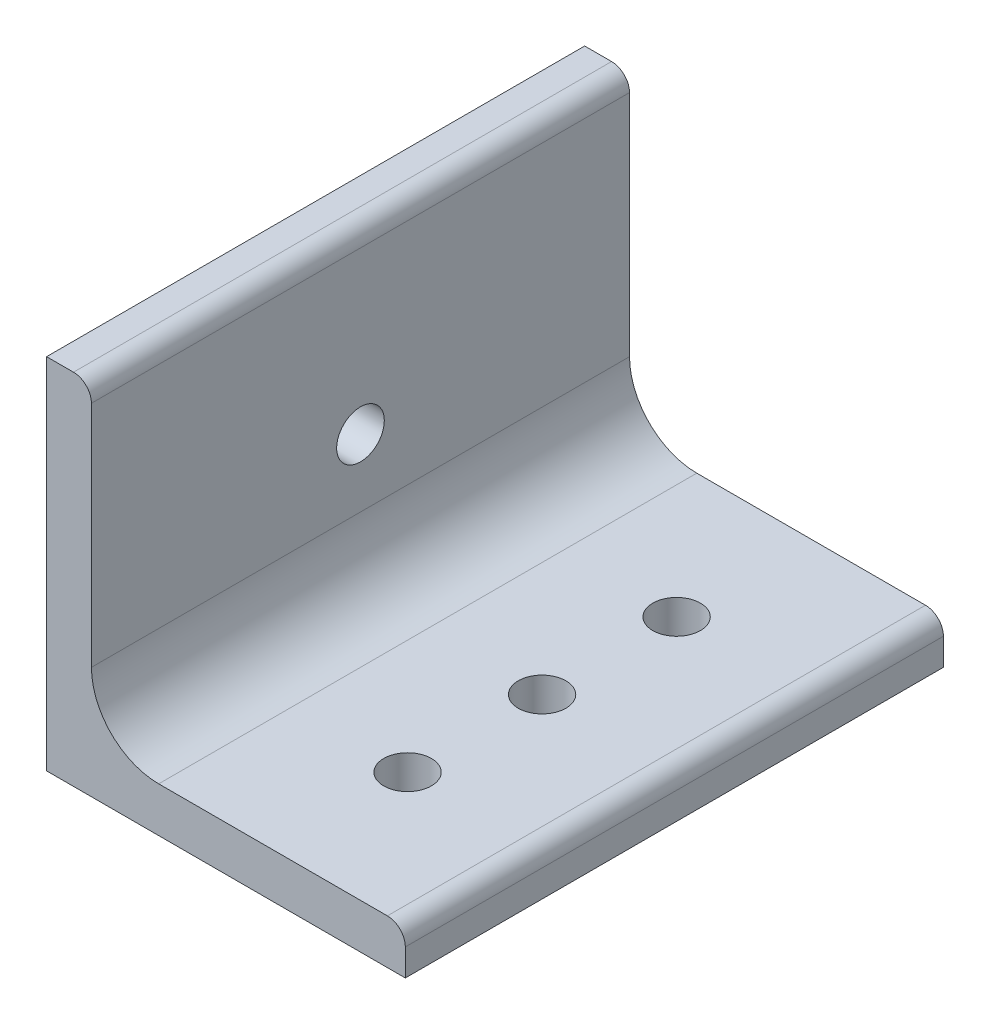
SolidWorks part; units mm, degrees
ref_plane "Front" through (0, 0, 0) normal (0, 0, 1) x (1, 0, 0)
ref_plane "Top" through (0, 0, 0) normal (0, 1, 0) x (1, 0, 0)
ref_plane "Right" through (0, 0, 0) normal (1, 0, 0) x (0, 0, -1)
sketch "Sketch1" plane through (0, 0, 0) normal (0, 0, 1) x (1, 0, 0)
  line L0 (0, 0) -> (0, 88.9)
  line L1 (0, 88.9) -> (-12.7, 88.9)
  line L2 (-12.7, 88.9) -> (-12.7, -12.7)
  line L3 (-12.7, -12.7) -> (88.9, -12.7)
  line L4 (88.9, -12.7) -> (88.9, 0)
  line L5 (88.9, 0) -> (0, 0)
  dimension "Outside Height" = 101.6
  dimension "Outside Width" = 101.6
  dimension "Wall Thickness" = 12.7
  dimension "Inside Width" = 88.9
  dimension "Inside Height" = 88.9
sketch "Sketch2" plane through (0, 0, 0) normal (1, 0, 0) x (0, 0, -1)
  line L0 (-76.2, 0) -> (76.2, 0) construction
  line L1 (76.2, -12.7) -> (-76.2, -12.7) construction
  point P2 (0, 0)
  point P3 (0, -12.7)
  point P5 (76.2, 0)
  point P6 (35.56, -12.7)
  point P9 (0, -12.7)
  point P10 (-76.2, -12.7)
  point P11 (76.2, -12.7)
  point P12 (-76.2, 0)
  point P14 (-35.56, -12.7)
  dimension "Length" = 152.4
  dimension "D1" = 111.76
  dimension "D2" = 111.76
sketch "Sketch3" plane through (0, 0, 0) normal (0, 0, 1) x (1, 0, 0)
  line L0 (0, 0) -> (0, 88.9) construction
  line L1 (0, 88.9) -> (-12.7, 88.9) construction
  line L2 (-12.7, 88.9) -> (-12.7, -12.7) construction
  line L3 (-12.7, -12.7) -> (88.9, -12.7) construction
  line L4 (88.9, -12.7) -> (88.9, 0) construction
  line L5 (88.9, 0) -> (0, 0) construction
  line L6 (0, 19.05) -> (0, 83.82)
  line L7 (-5.08, 88.9) -> (-12.7, 88.9)
  line L8 (-12.7, 88.9) -> (-12.7, -12.7)
  line L9 (-12.7, -12.7) -> (88.9, -12.7)
  line L10 (88.9, -12.7) -> (88.9, -5.08)
  line L11 (83.82, 0) -> (19.05, 0)
  arc A0 (0, 19.05) -> (19.05, 0) centre (19.05, 19.05) ccw
  arc A1 (88.9, -5.08) -> (83.82, 0) centre (83.82, -5.08) ccw
  arc A2 (0, 83.82) -> (-5.08, 88.9) centre (-5.08, 83.82) ccw
  dimension "D1" = 5.08
  dimension "D2" = 19.05
extrude "Boss-Extrude1" add sketch "Sketch3" along normal up to vertex (76.2 mm away) and the other way up to vertex (76.2 mm away) up to point (0, 0, 76.2) other way up to point (0, 0, -76.2)
sketch "Sketch4" plane through (0, 0, 0) normal (1, 0, 0) x (0, 0, -1)
  line L0 (-76.2, -12.7) -> (76.2, -12.7) construction
  line L1 (0, 55.88) -> (0, -55.88) construction
  point P0 (0, 38.1)
  dimension "D1" = 50.8
hole_wizard "M12 Clearance Hole1" positions "Sketch4" profile "Sketch5" hole size "M12" standard "ANSI Metric" end condition through all
sketch "Sketch5" plane through (0, 38.1, 0) normal (0, 1, 0) x (0, 0, -1)
  line L0 (0, 0) -> (0, 12.7)
  line L1 (0, 12.7) -> (6.75, 12.7)
  line L2 (6.75, 12.7) -> (6.75, 0)
  line L5 (6.75, 0) -> (0, 0)
  line L11 (0, -6.35) -> (0, 107.95) construction
  dimension "Thru Hole Dia." = 13.5
  dimension "Thru Hole Depth" = 12.7
sketch "Sketch6" plane through (0, 0, 0) normal (0, 1, 0) x (1, 0, 0)
  line L0 (83.82, 76.2) -> (19.05, 76.2) construction
  line L1 (51.435, 76.2) -> (51.435, 38.1) construction
  line L2 (51.435, 38.1) -> (51.435, 0) construction
  line L3 (51.435, 0) -> (51.435, -38.1) construction
  line L4 (51.435, -38.1) -> (51.435, -76.2) construction
  line L5 (83.82, -76.2) -> (19.05, -76.2) construction
  point P12 (51.435, 38.1)
  point P13 (51.435, 0)
  point P14 (51.435, -38.1)
hole_wizard "1/2 Clearance Hole1" positions "Sketch6" profile "Sketch7" hole size "1/2" standard "ANSI Inch" end condition through all
sketch "Sketch7" plane through (51.435, 0, 38.1) normal (1, 0, 0) x (0, 0, 1)
  line L0 (0, 0) -> (0, 12.7)
  line L1 (0, 12.7) -> (6.7462, 12.7)
  line L2 (6.7462, 12.7) -> (6.7462, 0)
  line L5 (6.7462, 0) -> (0, 0)
  line L11 (0, -6.35) -> (0, 107.95) construction
  dimension "Thru Hole Dia." = 13.4925
  dimension "Thru Hole Depth" = 12.7
equation "\"D1@Sketch3\"=\"Wall Thickness@Sketch1\"*0.4"
equation "\"D2@Sketch3\"=\"Wall Thickness@Sketch1\"*1.5"
equation "\"D1@Sketch2\" = \"Outside Width@Sketch1\" * 1.1"
equation "\"D2@Sketch2\"=\"D1@Sketch2\""
